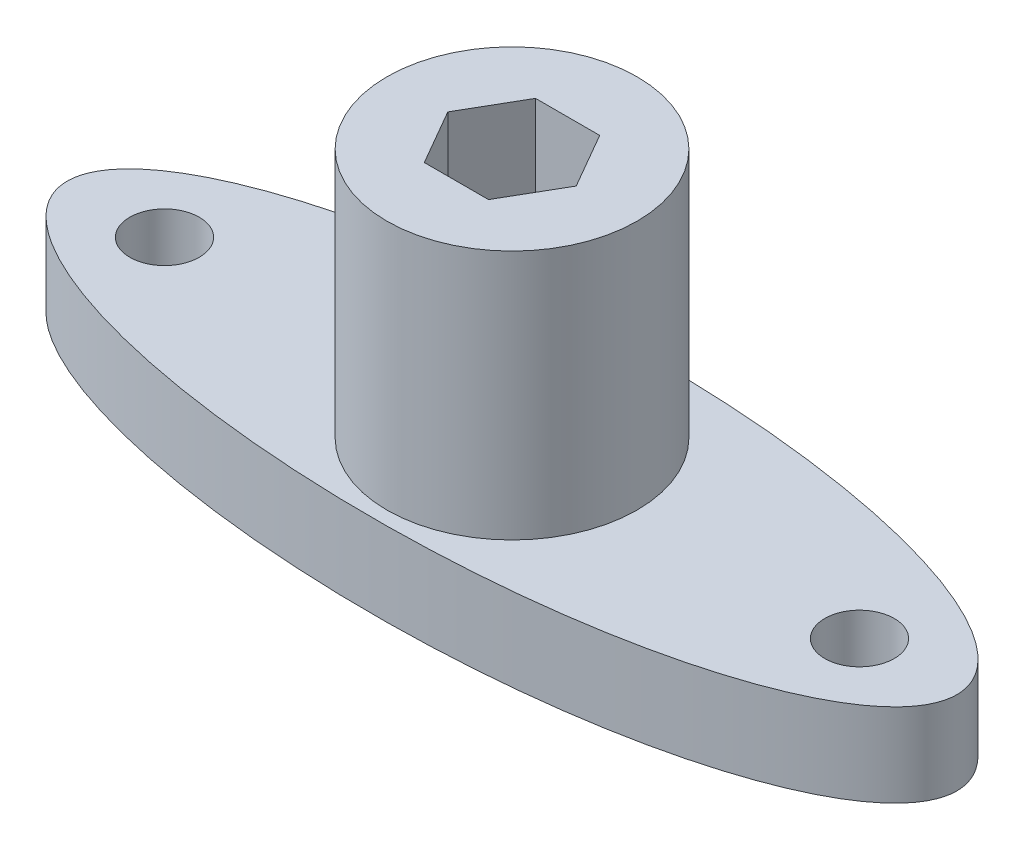
SolidWorks part; units mm, degrees
material "ABS PC"
ref_plane "Front Plane" through (0, 0, 0) normal (0, 0, 1) x (1, 0, 0)
ref_plane "Top Plane" through (0, 0, 0) normal (0, 1, 0) x (1, 0, 0)
ref_plane "Right Plane" through (0, 0, 0) normal (1, 0, 0) x (0, 0, -1)
sketch "Sketch1" plane through (0, 0, 0) normal (0, 1, 0) x (1, 0, 0)
  line L1 (2.9329, 0) -> (1.4665, 2.54)
  line L2 (1.4665, 2.54) -> (-1.4665, 2.54)
  line L3 (-1.4665, 2.54) -> (-2.9329, 0)
  line L4 (-2.9329, 0) -> (-1.4665, -2.54)
  line L5 (-1.4665, -2.54) -> (1.4665, -2.54)
  line L6 (1.4665, -2.54) -> (2.9329, 0)
  circle A0 centre (-15.875, 0) radius 1.5875
  circle A1 centre (15.875, 0) radius 1.5875
  circle A2 centre (0, 0) radius 5.715
  circle A3 centre (0, 0) radius 2.54 construction
  ellipse E0 centre (0, 0) end of major axis (20.32, 0) minor radius 6.35
  point P9 (0, 0)
  dimension "D3" = 3.175
  dimension "D6" = 11.43
  dimension "D1" = 40.64
  dimension "D2" = 12.7
  dimension "D4" = 4.445
  dimension "D5" = 4.445
  dimension "D7" = 5.08
extrude "Boss-Extrude1" add sketch "Sketch1" along normal blind 3.81 contours E0 A0 A1 A2 | A2 L6 L5 L4 L3 L2 L1 | L5 L6 L1 L2 L3 L4 region at (0, 0, 0) region at (-5.5534, 0, 0) region at (-19.8839, 0, 0.179)
extrude "Boss-Extrude2" add sketch "Sketch1<3>" along normal blind 3.81 from surface contours L5 L6 L1 L2 L3 L4 | A2 L6 L5 L4 L3 L2 L1 region at (0, 0, 0) region at (-5.5534, 0, 0) starting at face at (-15.875, 3.81, 1.5875)
sketch "Sketch1<3>" plane through (0, 0, 0) normal (0, 1, 0) x (1, 0, 0) same geometry as "Sketch1"
extrude "Boss-Extrude3" add sketch "Sketch1<4>" along normal blind 11.43 from surface contours A2 L6 L5 L4 L3 L2 L1 region at (-5.5534, 0, 0) starting at face at (0, 3.81, 5.715)
sketch "Sketch1<4>" plane through (0, 0, 0) normal (0, 1, 0) x (1, 0, 0) same geometry as "Sketch1"
